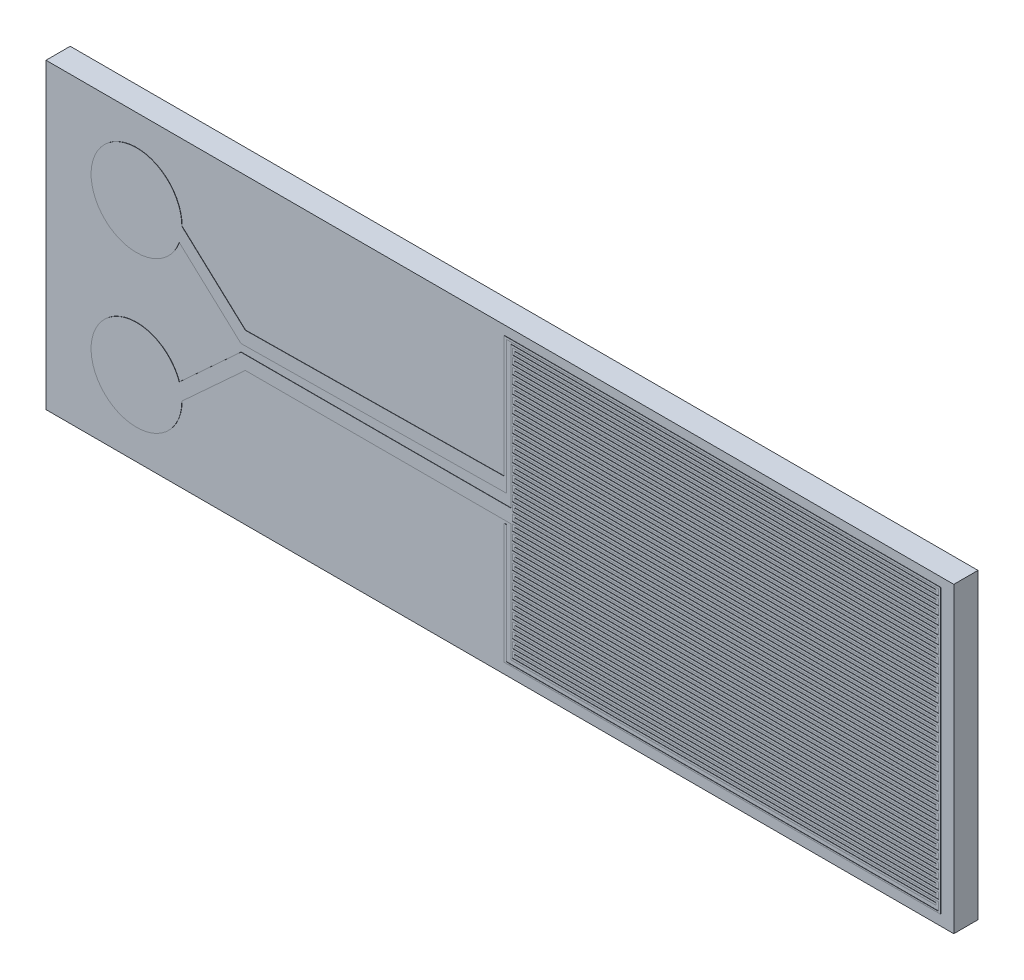
SolidWorks part; units mm, degrees
ref_plane "Front" through (0, 0, 0) normal (0, 0, 1) x (1, 0, 0)
ref_plane "Top" through (0, 0, 0) normal (0, 1, 0) x (1, 0, 0)
ref_plane "Right" through (0, 0, 0) normal (1, 0, 0) x (0, 0, -1)
sketch "草图1" plane through (0, 0, 0) normal (0, 0, 1) x (1, 0, 0)
  line L1 (0, 0) -> (30, 0)
  line L2 (0, 0) -> (0, 10)
  line L3 (0, 10) -> (30, 10)
  line L4 (30, 0) -> (30, 10)
  dimension "D1" = 10
  dimension "D2" = 30
extrude "凸台-拉伸1" add sketch "草图1" along normal blind 0.8
sketch "草图2" plane through (0, 0, 0.8) normal (0, 0, 1) x (1, 0, 0)
  line L0 (30, 10) -> (0, 10) construction
  line L1 (15.5, 9.7) -> (29.5, 9.7)
  line L2 (15.5, 9.7) -> (15.5, 9.63)
  line L3 (15.5, 9.63) -> (29.5, 9.63)
  line L4 (29.5, 9.7) -> (29.5, 9.63)
  line L5 (30, 0) -> (30, 10) construction
  dimension "D1" = 0.3
  dimension "D2" = 0.5
  dimension "D3" = 0.07
  dimension "D4" = 14
extrude "凸台-拉伸2" add sketch "草图2" along normal blind 0.01
pattern_linear "阵列(线性)1" count 33 spacing 0.28 along (0, -1, 0) of "凸台-拉伸2"
sketch "草图3" plane through (0, 0, 0.8) normal (0, 0, 1) x (1, 0, 0)
  line L0 (15.5, 9.7) -> (15.5, 9.63) construction
  line L1 (15.42, 9.56) -> (29.42, 9.56)
  line L2 (15.42, 9.56) -> (15.42, 9.49)
  line L3 (15.42, 9.49) -> (29.42, 9.49)
  line L4 (29.42, 9.56) -> (29.42, 9.49)
  line L5 (15.5, 9.63) -> (29.5, 9.63) construction
  line L8 (29.5, 9.63) -> (29.5, 9.7) construction
  line L12 (29.5, 9.42) -> (15.5, 9.42) construction
  line L13 (29.5, 9.7) -> (15.5, 9.7) construction
  point P4 (15.42, 9.525)
  point P7 (15.5, 9.665)
  point P12 (29.5, 9.665)
  dimension "D1" = 0.08
  dimension "D2" = 0.07
  dimension "D3" = 0.07
  dimension "D4" = 0.08
  dimension "D5" = 0.28
extrude "凸台-拉伸3" add sketch "草图3" along normal blind 0.01
pattern_linear "阵列(线性)2" count 33 spacing 0.28 along (0, -1, 0) of "凸台-拉伸3"
sketch "草图5" plane through (0, 0, 0.8) normal (0, 0, 1) x (1, 0, 0)
  line L0 (0, 0) -> (30, 0) construction
  line L1 (15.15, 9.7) -> (29.57, 9.7)
  line L2 (15.15, 9.7) -> (15.15, 0.35)
  line L3 (15.15, 0.35) -> (29.57, 0.35)
  line L4 (29.57, 9.7) -> (29.57, 0.35)
  line L5 (15.22, 0.4) -> (29.5, 0.4)
  line L6 (15.15, 0.57) -> (15.15, 0.35)
  line L7 (15.15, 0.35) -> (29.57, 0.35)
  line L8 (29.57, 0.66) -> (29.57, 0.35)
  line L9 (29.57, 0.35) -> (19.5, 0.35)
  line L10 (29.57, 0.35) -> (29.57, 9.7)
  line L11 (29.57, 9.7) -> (29.5, 9.7)
  line L12 (29.5, 0.4) -> (29.5, 9.7)
  line L13 (15.42, 3.12) -> (15.42, 3.05) construction
  line L14 (29.5, 1.51) -> (29.5, 1.58) construction
  line L15 (29.5, 1.51) -> (29.5, 1.58)
  line L16 (29.5, 9.7) -> (15.5, 9.7) construction
  line L17 (29.5, 9.7) -> (15.5, 9.7)
  line L20 (15.15, 0.57) -> (15.15, 9.7)
  line L21 (15.15, 9.7) -> (8.97, 9.7)
  line L22 (15.22, 0.4) -> (15.22, 9.63)
  line L23 (15.15, 9.7) -> (15.5, 9.7)
  line L24 (15.15, 9.7) -> (15.15, 9.36)
  line L25 (15.22, 9.63) -> (15.5, 9.63)
  line L26 (15.5, 9.7) -> (15.5, 9.63)
  dimension "D1" = 0.07
  dimension "D2" = 0.35
  dimension "D3" = 0.05
  dimension "D4" = 0.2
  dimension "D5" = 0.07
extrude "凸台-拉伸4" add sketch "草图5" along normal blind 0.01 contours L26 L1 L2 L20 L3 L7 L4 L12 L5 L22 L25 region at (15.325, 9.6828, 0.8)
sketch "草图6" plane through (0, 0, 0.8) normal (0, 0, 1) x (1, 0, 0)
  line L1 (15.42, 0.53) -> (29.42, 0.53) construction
  line L2 (29.42, 9.56) -> (15.42, 9.56) construction
  line L3 (15.42, 9.56) -> (15.42, 9.49) construction
  line L4 (0, 10) -> (0, 0)
  line L5 (0, 0) -> (30, 0)
  line L6 (30, 0) -> (30, 10)
  line L7 (30, 10) -> (0, 10)
  line L8 (0, 10) -> (0, 0)
  line L9 (0, 0) -> (30, 0)
  line L10 (30, 0) -> (30, 10)
  line L11 (30, 10) -> (0, 10)
  line L13 (29.42, 9.56) -> (15.42, 9.56)
  line L14 (15.42, 9.56) -> (15.42, 9.49)
  line L16 (15.42, 0.53) -> (15.37, 0.53)
  line L17 (15.42, 0.53) -> (15.42, 9.56)
  line L18 (15.42, 9.56) -> (15.37, 9.56)
  line L19 (15.37, 0.53) -> (15.37, 9.56)
  dimension "D2" = 0.05
  dimension "D1" = 0
extrude "凸台-拉伸5" add sketch "草图6" along normal blind 0.01 contours L19 L16 L17 L14 L18 region at (15.395, 5.045, 0.8)
sketch "草图9" plane through (0, 0, 0.8) normal (0, 0, 1) x (1, 0, 0)
  line L0 (0, 10) -> (0, 0) construction
  line L1 (0, 0) -> (30, 0) construction
  line L2 (6.5967, 4.425) -> (4.5, 2.5)
  line L3 (6.4518, 4.875) -> (4.4131, 3.0032)
  line L4 (6.4518, 5.125) -> (15.15, 5.2253)
  line L5 (6.5967, 5.575) -> (15.15, 5.6753)
  line L6 (6.5967, 5.575) -> (4.5, 7.5)
  line L7 (6.7782, 5) -> (0, 5) construction
  line L8 (15.37, 0.53) -> (15.37, 9.56) construction
  line L9 (6.4518, 4.875) -> (15.37, 4.875)
  line L10 (6.4518, 5.125) -> (4.4131, 6.9968)
  line L11 (15.15, 5.2253) -> (15.15, 5.6753)
  line L12 (15.15, 9.7) -> (15.15, 0.35) construction
  line L13 (6.5967, 4.425) -> (15.37, 4.425)
  line L14 (15.37, 4.875) -> (15.37, 4.425)
  line L15 (15.37, 0.53) -> (15.37, 9.56)
  line L16 (15.15, 9.7) -> (15.15, 0.35) construction
  circle A0 centre (3, 2.5) radius 1.5
  circle A1 centre (3, 7.5) radius 1.5
  point P17 (0, 0)
  line M44 (15.15, 0.35) -> (15.15, 9.7)
  dimension "D1" = 3
  dimension "D3" = 2.5
  dimension "D2" = 3
  dimension "D4" = 0.25
  dimension "D5" = 0.45
  dimension "D6" = 2.1836
ref_plane "基准面1" through (0, 5, 0) normal (0, -1, 0) x (-1, 0, 0)
extrude "凸台-拉伸7" add sketch "草图9" along normal blind 0.01 contours A0 L2 L13 L9 L3 M44 | L14 L9 L13 M44 | L6 A1 L10 L4 L5 M44 | A0 | A1 region at (10.7996, 5.2851, 0.8) region at (9.5775, 4.4277, 0.8) region at (3, 2.5, 0.8) region at (15.26, 4.65, 0.8) region at (3, 7.5, 0.8)
sketch "草图10" plane through (15.15, 0, 0) normal (-1, 0, 0) x (0, 0, 1)
  line L0 (0.81, 4.425) -> (0.81, 0.35) construction
  line L1 (0.81, 5.2253) -> (0.8, 5.2253) construction
  line L2 (0.8, 5.2253) -> (0.8, 4.875)
  line L3 (0.8, 4.875) -> (0.81, 4.875)
  line L4 (0.81, 5.2253) -> (0.81, 4.875)
  line L5 (0.81, 5.2253) -> (0.81, 4.875) construction
  line L6 (0.8, 4.875) -> (0.81, 4.875) construction
  line L7 (0.8, 4.425) -> (0.81, 4.425)
  line L8 (0.8, 4.425) -> (0.8, 4.325)
  line L9 (0.8, 4.325) -> (0.81, 4.325)
  line L10 (0.81, 4.425) -> (0.81, 4.325)
  line L11 (0.8, 4.875) -> (0.81, 4.875)
  line L12 (0.81, 5.2253) -> (0.8, 5.2253)
  line M1 (0.81, 4.425) -> (0.8, 4.425)
  line M2 (0.8, 4.425) -> (0.8, 0.35)
  line M4 (0.81, 0.35) -> (0.81, 4.425)
  dimension "D1" = 0.1
extrude "切除-拉伸2" cut sketch "草图10" against normal blind 0.1 contours L9 M2 M4 M1 | L2 L3 L4 L12 region at (15.15, 4.375, 0.805)
sketch "草图11" plane through (0, 0, 0.8) normal (0, 0, 1) x (1, 0, 0)
  line L1 (0, 10) -> (0, 0)
  line L4 (0, 10) -> (0, 0) construction
  line L5 (5.7971, 5) -> (2.8033, 5) construction
  circle A0 centre (3, 2.5) radius 1.5 construction
  circle A2 centre (3, 2.5) radius 0.65
  point P0 (0, 0)
  point P8 (0, 5)
extrude "切除-拉伸4" cut sketch "草图11" against normal through all contours A2 region at (3, 2.5, 0.8)
